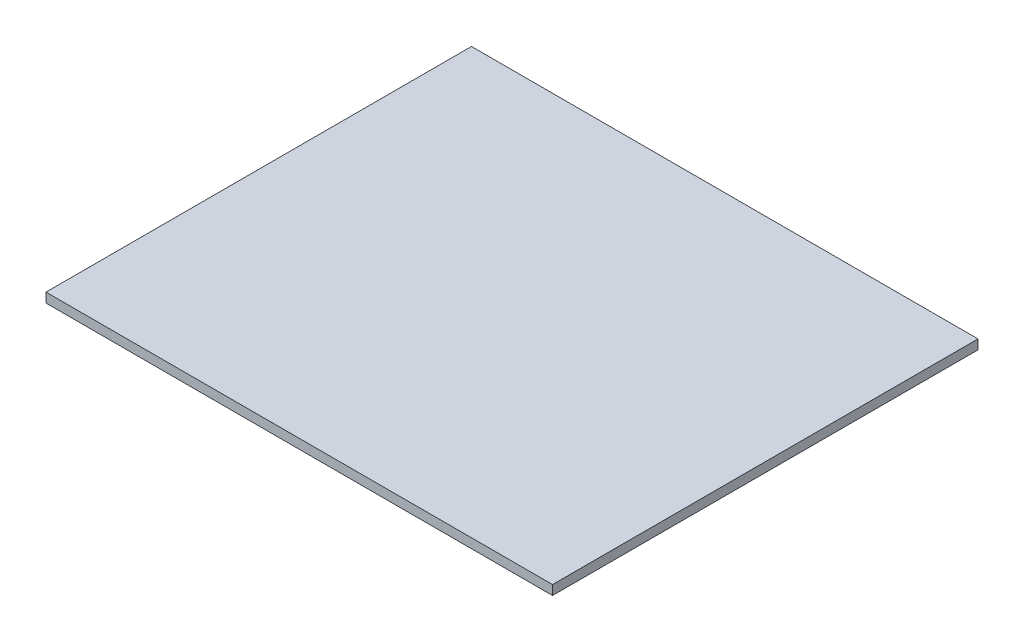
SolidWorks part; units mm, degrees
ref_plane "Front Plane" through (0, 0, 0) normal (0, 0, 1) x (1, 0, 0)
ref_plane "Top Plane" through (0, 0, 0) normal (0, 1, 0) x (1, 0, 0)
ref_plane "Right Plane" through (0, 0, 0) normal (1, 0, 0) x (0, 0, -1)
sketch "Sketch1" plane through (0, 0, 0) normal (0, 1, 0) x (1, 0, 0)
  line L1 (-317.5, -266.7) -> (317.5, -266.7)
  line L2 (-317.5, -266.7) -> (-317.5, 266.7)
  line L3 (-317.5, 266.7) -> (317.5, 266.7)
  line L4 (317.5, -266.7) -> (317.5, 266.7)
  line L5 (-317.5, -266.7) -> (317.5, 266.7) construction
  line L6 (-317.5, 266.7) -> (317.5, -266.7) construction
  point P0 (0, 0)
  dimension "D1" = 635
  dimension "D2" = 533.4
extrude "Boss-Extrude1" add sketch "Sketch1" along normal blind 11.9062
